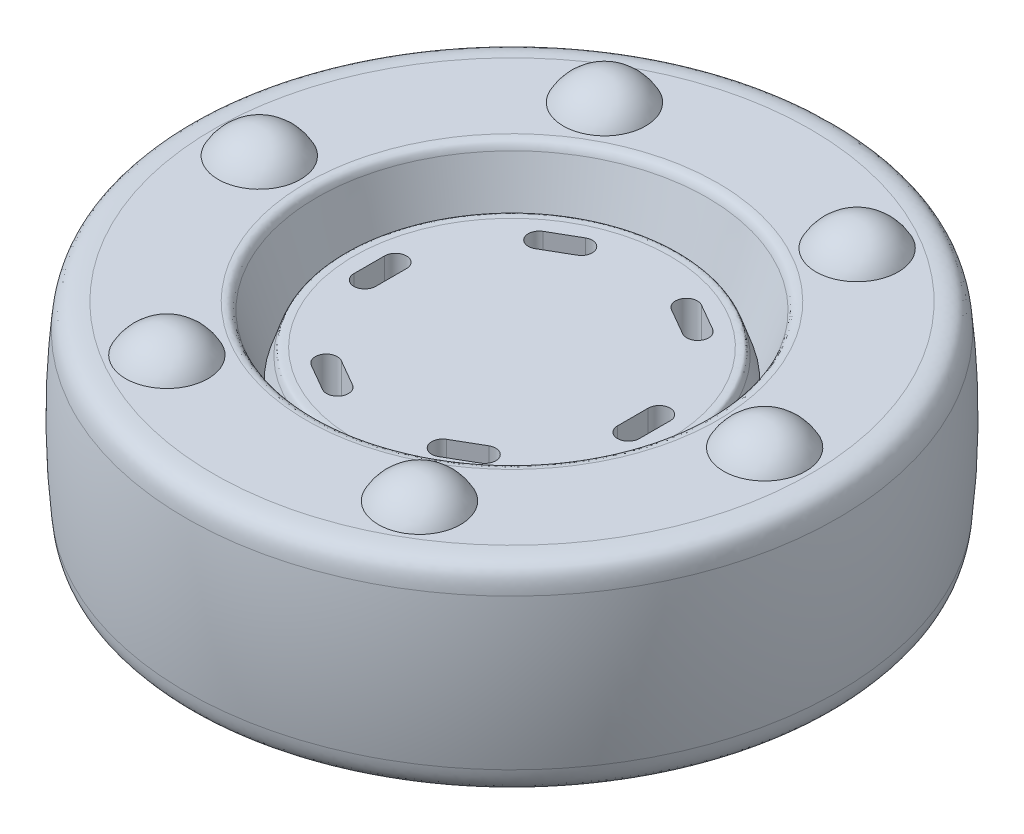
SolidWorks part; units mm, degrees
ref_plane "Front Plane" through (0, 0, 0) normal (0, 0, 1) x (1, 0, 0)
ref_plane "Top Plane" through (0, 0, 0) normal (0, 1, 0) x (1, 0, 0)
ref_plane "Right Plane" through (0, 0, 0) normal (1, 0, 0) x (0, 0, -1)
sketch "Sketch1" plane through (0, 0, 0) normal (0, 0, 1) x (1, 0, 0)
  line L0 (0, 6.985) -> (19.177, 6.985)
  line L1 (19.177, 6.985) -> (20.2476, 3.81)
  line L2 (20.2476, 3.81) -> (22.86, 11.557)
  line L3 (22.86, 11.557) -> (37.338, 11.557)
  line L4 (19.177, 6.985) -> (21.3183, 6.985) construction
  line L5 (20.2476, 6.985) -> (20.2476, 3.81) construction
  line L6 (0, 0) -> (38.1, 0)
  line L7 (0, 0) -> (0, 6.985)
  arc A0 (37.338, 11.557) -> (38.1, 0) centre (-49.9216, 0) cw
  dimension "D1" = 11.557
  dimension "D2" = 4.572
  dimension "D3" = 22.86
  dimension "D4" = 37.338
  dimension "D5" = 19.177
  dimension "D6" = 3.81
  dimension "D7" = 38.1
revolve "Revolve1" add sketch "Sketch1" angle 360 about L7
fillet "Fillet1" radius 3.175 1 edges at (0, 11.557, -37.338) conic rho 0.6
sketch "Sketch2" plane through (0, 0, 0) normal (0, 0, 1) x (1, 0, 0)
  line L0 (29.21, 14.478) -> (29.21, 3.81)
  circle A0 centre (29.21, 9.144) radius 5.334
  dimension "D2" = 10.668
  dimension "D1" = 14.478
  dimension "D3" = 29.21
revolve "Revolve4" add sketch "Sketch2" angle 360 about L0 region at (31.4738, 9.144, 0)
fillet "Fillet2" radius 1.27 1 edges at (0, 11.557, -22.86) conic rho 0.6
sketch "Sketch3" plane through (0, 6.985, 0) normal (0, 1, 0) x (1, 0, 0)
  line L0 (15.24, 1.778) -> (15.24, -1.778) construction
  line L1 (16.51, 1.778) -> (16.51, -1.778)
  line L2 (13.97, 1.778) -> (13.97, -1.778)
  arc A0 (16.51, 1.778) -> (13.97, 1.778) centre (15.24, 1.778) ccw
  arc A1 (13.97, -1.778) -> (16.51, -1.778) centre (15.24, -1.778) ccw
  point P2 (15.24, 0)
  point P7 (15.24, 3.048)
  point P8 (15.24, -3.048)
  point P10 (0, 0)
  dimension "D1" = 13.97
  dimension "D2" = 16.51
  dimension "D3" = 6.096
extrude "Cut-Extrude1" cut sketch "Sketch3" against normal through all
fillet "Fillet3" radius 1.27 1 edges at (0, 6.985, -19.177) conic rho 0.8
pattern_circular "CirPattern1" count 6 over 360 about axis through (0, 0, 0) along (0, 1, 0) of "Cut-Extrude1", "Revolve4"
mirror "Mirror1" about plane through (0, 0, 0) normal (0, 1, 0) of bodies 106
